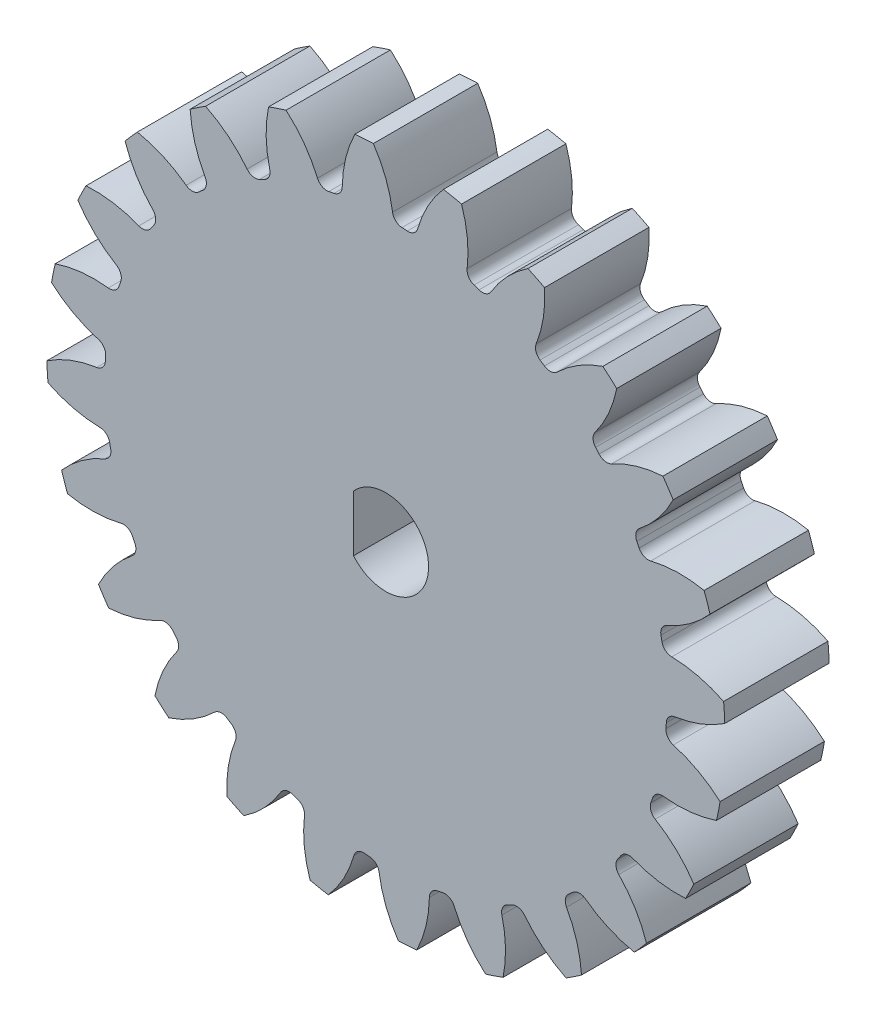
SolidWorks part; units mm, degrees
ref_plane "Front" through (0, 0, 0) normal (0, 0, 1) x (1, 0, 0)
ref_plane "Top" through (0, 0, 0) normal (0, 1, 0) x (1, 0, 0)
ref_plane "Right" through (0, 0, 0) normal (1, 0, 0) x (0, 0, -1)
sketch "Sketch3" plane through (0, 0, 0) normal (0, 0, 1) x (1, 0, 0)
  circle A0 centre (0, 0) radius 20.6375
  dimension "od" = 41.275
extrude "gearBody" add sketch "Sketch3" along normal blind 6.35
sketch "Sketch2" plane through (0, 0, 0) normal (0, 0, 1) x (1, 0, 0)
  line L0 (0, 0) -> (16.5385, 6.8505) construction
  line L1 (22.0347, -5.709) -> (0, 0) construction
  line L2 (0, 0) -> (36.3143, 0) construction
  line L3 (19.05, -0.043) -> (18.8852, -2.5004) construction
  line L5 (18.9676, -1.2717) -> (0, 0) construction
  line L7 (0, 0) -> (17.9011, 0) construction
  arc A0 (17.8975, -0.3593) -> (17.7853, -2.0332) centre (0, 0) ccw construction
  arc A1 (20.6236, 0.7563) -> (20.3381, -3.5027) centre (0, 0) ccw construction
  arc A2 (19.05, -0.043) -> (18.8852, -2.5004) centre (0, 0) ccw construction
  arc A3 (17.0444, -1.304) -> (17.0659, -0.983) centre (0, 0) ccw
  arc A4 (22.0347, -5.709) -> (17.4884, -1.9416) centre (15.476, -8.9969) ccw
  arc A5 (22.0347, -5.709) -> (22.5996, 2.7164) centre (0, 0) ccw
  arc A6 (22.5996, 2.7164) -> (17.5911, -0.4103) centre (16.5385, 6.8505) cw
  arc A7 (17.0659, -0.983) -> (17.5911, -0.4103) centre (17.6793, -1.0183) cw
  arc A8 (17.4884, -1.9416) -> (17.0444, -1.304) centre (17.657, -1.3509) cw
  point P6 (22.5996, 2.7164)
  point P22 (22.0347, -5.709)
  dimension "baseDia" = 35.8023
  dimension "od" = 41.275
  dimension "pd" = 38.1
  dimension "rd" = 34.1884
  dimension "rFillet" = 0.6144
  dimension "pointX" = 22.5996
  dimension "pointY" = 2.7164
  dimension "CTT" = 2.4574
  dimension "flankCenterAngle" = 22.5
extrude "toothCut" cut sketch "Sketch2" along normal through all
pattern_circular "CirPattern1" count 24 over 360 about axis through (0, 0, 6.35) along (0, 0, -1) of "toothCut"
sketch "hub1Dia" plane through (0, 0, 0) normal (0, 0, -1) x (-1, 0, 0)
  circle A0 centre (0, 0) radius 12.7
  dimension "hub1Dia" = 25.4
sketch "hub2Dia" plane through (0, 0, 6.35) normal (0, 0, 1) x (1, 0, 0)
  circle A0 centre (0, 0) radius 12.7
  dimension "hub2dia" = 25.4
sketch "boreDia" plane through (0, 0, 0) normal (0, 0, 1) x (1, 0, 0)
  circle A0 centre (0, 0) radius 6.35
  dimension "boreDia" = 12.7
sketch "Sketch4" plane through (0, 0, 0) normal (0, 0, -1) x (-1, 0, 0)
  line L0 (1.9685, -1.7039) -> (1.9685, 1.7039)
  line L1 (-2.6035, 4.8001) -> (-2.6035, -4.732) construction
  arc A0 (1.9685, 1.7039) -> (1.9685, -1.7039) centre (0, 0) ccw
  dimension "D1" = 5.207
  dimension "D2" = 4.572
extrude "Cut-Extrude1" cut sketch "Sketch4" against normal through all
sketch "Sketch5" plane through (0, 0, 0) normal (0, 1, 0) x (1, 0, 0)
  line L0 (0, 0) -> (0, 6.4123) construction
sketch "Sketch6" plane through (0, 0, 0) normal (0, 0, 1) x (1, 0, 0)
  circle A0 centre (0, 0) radius 2.6035 construction
equation "\"tightTol\"= 0.005in"
equation "\"normTol\"= 0.01in"
equation "\"looseTol\"= 0.02in"
equation "\"D1@Sketch4\"=\"tightTol\"+0.2in"
equation "\"D2@Sketch4\"=\"tightTol\"+0.175"
